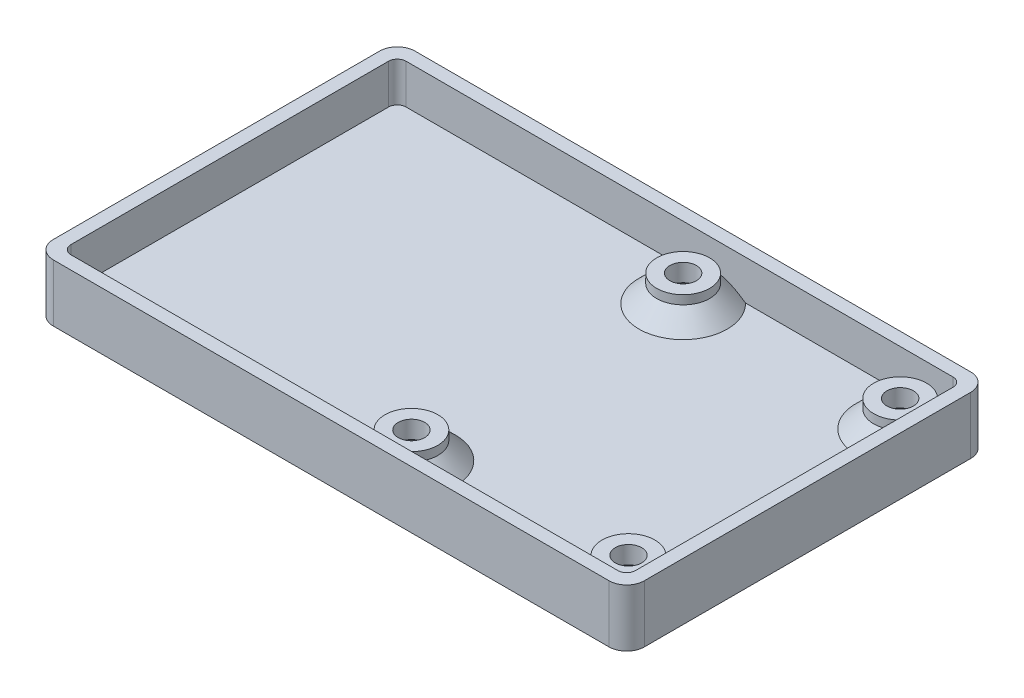
SolidWorks part; units mm, degrees
ref_plane "Спереди" through (0, 0, 0) normal (0, 0, 1) x (1, 0, 0)
ref_plane "Сверху" through (0, 0, 0) normal (0, 1, 0) x (1, 0, 0)
ref_plane "Справа" through (0, 0, 0) normal (1, 0, 0) x (0, 0, -1)
sketch "Эскиз1" plane through (0, 0, 0) normal (0, 1, 0) x (1, 0, 0)
  line L1 (-33.5, 20.5) -> (33.5, 20.5)
  line L2 (-33.5, 20.5) -> (-33.5, -20.5)
  line L3 (-33.5, -20.5) -> (33.5, -20.5)
  line L4 (33.5, 20.5) -> (33.5, -20.5)
  line L5 (-33.5, 20.5) -> (33.5, -20.5) construction
  line L6 (-33.5, -20.5) -> (33.5, 20.5) construction
  point P0 (0, 0)
  dimension "D1" = 41
  dimension "D2" = 67
extrude "Бобышка-Вытянуть1" add sketch "Эскиз1" along normal blind 6.5
sketch "Эскиз2" plane through (0, 6.5, 0) normal (0, 1, 0) x (1, 0, 0)
  line L1 (-32, 19) -> (32, 19)
  line L2 (-32, 19) -> (-32, -19)
  line L3 (-32, -19) -> (32, -19)
  line L4 (32, 19) -> (32, -19)
  line L5 (-32, 19) -> (32, -19) construction
  line L6 (-32, -19) -> (32, 19) construction
  point P0 (0, 0)
  dimension "D1" = 38
  dimension "D2" = 64
extrude "Вырез-Вытянуть1" cut sketch "Эскиз2" against normal blind 4.5
fillet "Скругление1" radius 1 4 edges at (-32, 4.25, 19) (32, 4.25, 19) (32, 4.25, -19) (-32, 4.25, -19)
fillet "Скругление2" radius 2 4 edges at (33.5, 3.25, 20.5) (33.5, 3.25, -20.5) (-33.5, 3.25, -20.5) (-33.5, 3.25, 20.5)
sketch "Эскиз3" plane through (0, 2, 0) normal (0, 1, 0) x (1, 0, 0)
  line L0 (-40.6812, 0) -> (41.4316, 0) construction
  line L1 (0, 27.3281) -> (0, -27.1442) construction
  circle A0 centre (28.6, 15.4) radius 3
  circle A1 centre (4, 15.4) radius 3
  circle A2 centre (4, -15.4) radius 3
  circle A3 centre (28.6, -15.4) radius 3
  dimension "D3" = 6
  dimension "D1" = 30.8
  dimension "D2" = 24.6
  dimension "D4" = 8
extrude "Бобышка-Вытянуть2" add sketch "Эскиз3" along normal blind 3
sketch "Эскиз4" plane through (0, 5, 0) normal (0, 1, 0) x (1, 0, 0)
  circle A0 centre (4, 15.4) radius 1.5
  circle A1 centre (28.6, 15.4) radius 1.5
  circle A2 centre (28.6, -15.4) radius 1.5
  circle A3 centre (4, -15.4) radius 1.5
  circle A4 centre (4, -15.4) radius 3 construction
  dimension "D1" = 3
extrude "Вырез-Вытянуть2" cut sketch "Эскиз4" against normal blind 6
chamfer "Фаска1" distance 3 angle 45 4 edges at (28.6, 0, 16.9) (4, 0, 16.9) (28.6, 0, -13.9) (4, 0, -13.9)
chamfer "Фаска2" distance 2 angle 45 4 edges at (28.6, 2, -12.4) (4, 2, -12.4) (28.6, 2, 18.4) (4, 2, 18.4)
